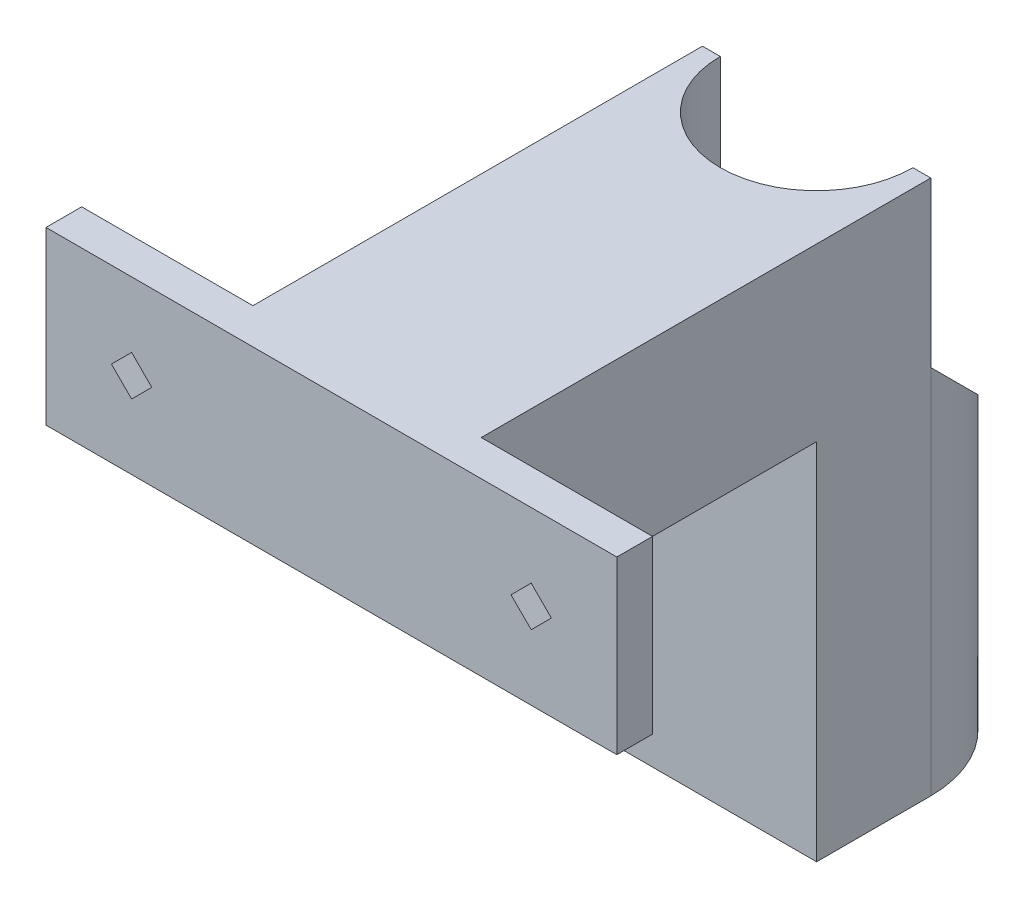
SolidWorks part; units mm, degrees
ref_plane "Front Plane" through (0, 0, 0) normal (0, 0, 1) x (1, 0, 0)
ref_plane "Top Plane" through (0, 0, 0) normal (0, 1, 0) x (1, 0, 0)
ref_plane "Right Plane" through (0, 0, 0) normal (1, 0, 0) x (0, 0, -1)
sketch "Sketch1" plane through (0, 0, 0) normal (0, 1, 0) x (1, 0, 0)
  circle A0 centre (0, 0) radius 13
  circle A1 centre (0, 0) radius 16
  dimension "D1" = 26
  dimension "D2" = 32
extrude "Boss-Extrude1" add sketch "Sketch1" along normal blind 2
sketch "Sketch2" plane through (0, 2, 0) normal (0, 1, 0) x (1, 0, 0)
  circle A0 centre (0, 0) radius 13.5
  circle A1 centre (0, 0) radius 16
  circle A2 centre (0, 0) radius 16 construction
  dimension "D1" = 27
extrude "Boss-Extrude2" add sketch "Sketch2" along normal blind 50
chamfer "Chamfer1" distance 0.5 angle 45 1 edges at (0, 2, 13)
sketch "Sketch3" plane through (0, 0, 0) normal (0, -1, 0) x (1, 0, 0)
  line L0 (-16, 0) -> (-16, 16)
  line L1 (-16, 16) -> (0, 16)
  line L2 (0, 16) -> (16, 16)
  line L3 (16, 16) -> (16, 0)
  line L4 (16, 0) -> (13.5, 0)
  line L5 (-16, 0) -> (-13.5, 0)
  circle A0 centre (0, 0) radius 16 construction
  circle A1 centre (0, 0) radius 13.5 construction
  arc A2 (13.5, 0) -> (-13.5, 0) centre (0, 0) ccw
  circle A3 centre (0, 0) radius 13.5 construction
  circle A4 centre (0, 0) radius 16 construction
extrude "Boss-Extrude3" add sketch "Sketch3" against normal blind 75
sketch "Sketch4" plane through (16, 0, 0) normal (1, 0, 0) x (0, 0, -1)
  line L1 (-16, 75) -> (-68, 75)
  line L2 (-16, 75) -> (-16, 51)
  line L3 (-16, 51) -> (-68, 51)
  line L4 (-68, 75) -> (-68, 51)
  dimension "D1" = 52
  dimension "D2" = 24
extrude "Boss-Extrude4" add sketch "Sketch4" against normal up to surface (32 mm away) up to face at (-16, 40.4, 6.4)
sketch "Sketch5" plane through (0, 0, 68) normal (0, 0, 1) x (1, 0, 0)
  line L0 (-16, 75) -> (-16, 51) construction
  line L1 (-16, 75) -> (-40, 75)
  line L2 (-16, 75) -> (-16, 51)
  line L3 (-16, 51) -> (-40, 51)
  line L4 (-40, 75) -> (-40, 51)
  line L5 (16, 51) -> (40, 51)
  line L6 (16, 51) -> (16, 75)
  line L7 (16, 75) -> (40, 75)
  line L8 (40, 51) -> (40, 75)
  line L9 (-16, 75) -> (16, 75) construction
  line L10 (-40, 75) -> (-16, 51) construction
  line L11 (-16, 75) -> (-40, 51) construction
  line L12 (16, 75) -> (40, 51) construction
  line L13 (40, 75) -> (16, 51) construction
  line L14 (-30.8284, 63) -> (-28, 65.8284)
  line L15 (-30.8284, 63) -> (-28, 60.1716)
  line L16 (-28, 65.8284) -> (-25.1716, 63)
  line L17 (-28, 60.1716) -> (-25.1716, 63)
  line L18 (-30.8284, 63) -> (-25.1716, 63) construction
  line L19 (-28, 65.8284) -> (-28, 60.1716) construction
  line L20 (25.1716, 63) -> (28, 65.8284)
  line L21 (25.1716, 63) -> (28, 60.1716)
  line L22 (28, 65.8284) -> (30.8284, 63)
  line L23 (28, 60.1716) -> (30.8284, 63)
  line L24 (25.1716, 63) -> (30.8284, 63) construction
  line L25 (28, 65.8284) -> (28, 60.1716) construction
  point P10 (-28, 63)
  point P15 (28, 63)
  point P16 (-28, 63)
  point P17 (28, 63)
  dimension "D1" = 24
  dimension "D2" = 24
  dimension "D3" = 4
  dimension "D4" = 4
  dimension "D5" = 4
  dimension "D6" = 4
extrude "Boss-Extrude5" add sketch "Sketch5" against normal blind 5
sketch "Sketch6" plane through (-16, 0, 0) normal (-1, 0, 0) x (0, 0, 1)
  line L0 (0, 52) -> (-16, 36)
  line L1 (-16, 52) -> (-16, 0) construction
  line L2 (-16, 36) -> (-16, 52)
  line L3 (-16, 52) -> (0, 52)
extrude "Cut-Extrude1" cut sketch "Sketch6" against normal through all
